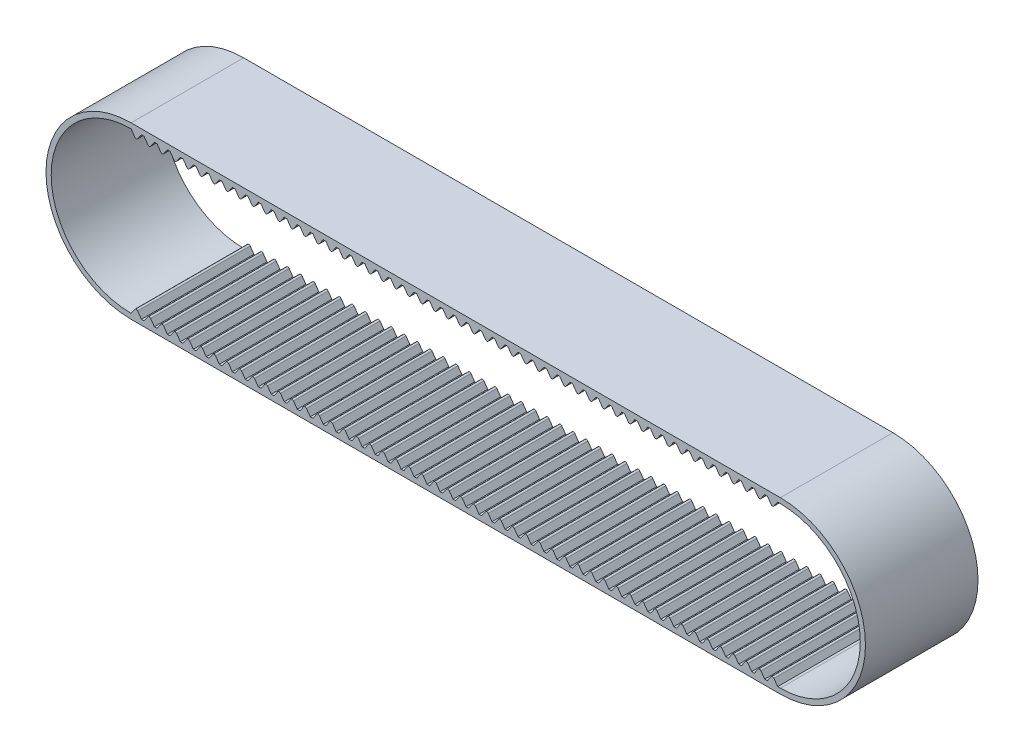
SolidWorks part; units mm, degrees
material "NEOPREN"
ref_plane "Ebene vorne" through (0, 0, 0) normal (0, 0, 1) x (1, 0, 0)
ref_plane "Ebene oben" through (0, 0, 0) normal (0, 1, 0) x (1, 0, 0)
ref_plane "Ebene rechts" through (0, 0, 0) normal (1, 0, 0) x (0, 0, -1)
sketch "Skizze1" plane through (0, 0, 0) normal (0, 0, 1) x (1, 0, 0)
  line L0 (37.5, 0) -> (-37.5, 0) construction
  line L1 (37.5, -9.83) -> (-37.5, -9.83)
  line L2 (37.5, 9.83) -> (-37.5, 9.83)
  arc A0 (37.5, -9.83) -> (37.5, 9.83) centre (37.5, 0) ccw
  arc A1 (-37.5, 9.83) -> (-37.5, -9.83) centre (-37.5, 0) ccw
  circle A2 centre (-37.5, 0) radius 9.83 construction
  circle A3 centre (37.5, 0) radius 9.83 construction
  point P2 (0, 0)
  point P12 (-27.67, 0)
  point P13 (27.67, 0)
  dimension "D1" = 75
  dimension "D2" = 19.66
  dimension "D3" = 55.34
extrude "Linear-Austragen-Dünn1" add sketch "Skizze1" along normal mid plane 13 thin thin type one direction reverse wall 0.6
sketch "Skizze2" plane through (0, 0, 6.5) normal (0, 0, 1) x (1, 0, 0)
  line L0 (-37.5, 9.23) -> (-36.31, 9.23)
  line L1 (37.5, 9.23) -> (-37.5, 9.23) construction
  line L2 (-36.31, 9.23) -> (-36.7413, 8.6152)
  line L3 (-37.0687, 8.6152) -> (-37.5, 9.23)
  line L4 (-36.905, 9.23) -> (-36.905, 8.3817) construction
  arc A0 (-36.7413, 8.6152) -> (-37.0687, 8.6152) centre (-36.905, 8.73) cw
  point P10 (-36.905, 8.53)
  dimension "D2" = 0.2
  dimension "D1" = 1.19
  dimension "D3" = 0.7
extrude "Aufsatz-Linear austragen1" add sketch "Skizze2" against normal up to surface (13 mm away) up to face at (0, 0, -6.5)
pattern_linear "Lineares Muster1" count 50 spacing 1.5 along (1, 0, 0) of "Aufsatz-Linear austragen1"
mirror "Spiegeln1" about plane through (0, 0, 0) normal (0, 1, 0) of "Lineares Muster1"
